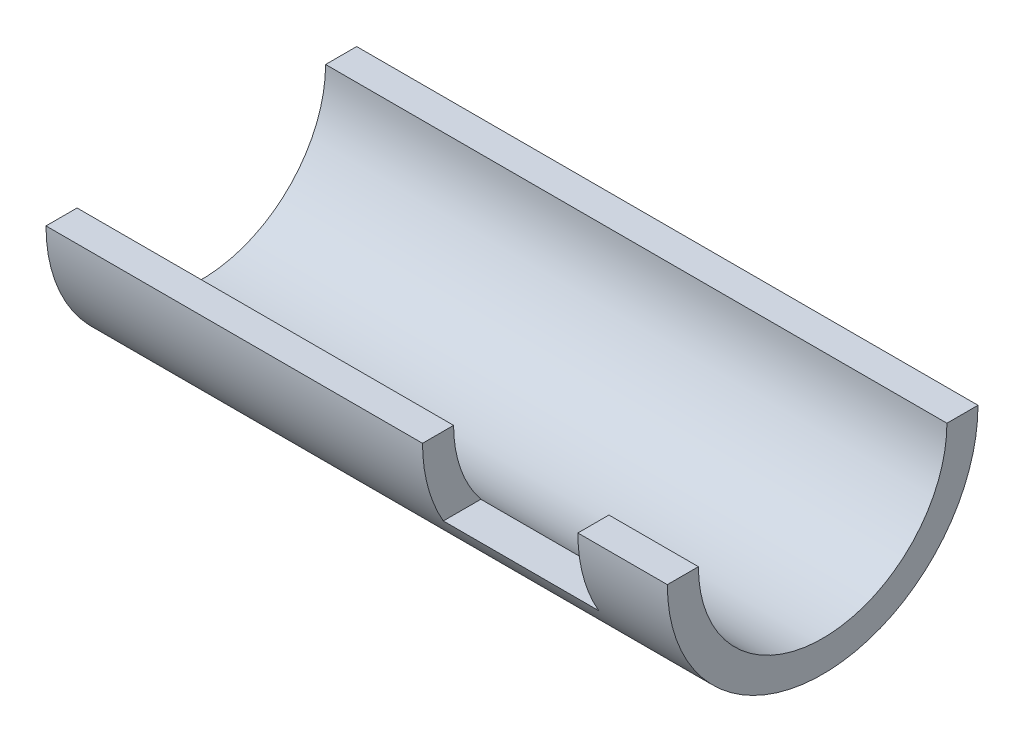
SolidWorks part; units mm, degrees
ref_plane "Front Plane" through (0, 0, 0) normal (0, 0, 1) x (1, 0, 0)
ref_plane "Top Plane" through (0, 0, 0) normal (0, 1, 0) x (1, 0, 0)
ref_plane "Right Plane" through (0, 0, 0) normal (1, 0, 0) x (0, 0, -1)
sketch "Sketch1" plane through (0, 0, 0) normal (1, 0, 0) x (0, 0, -1)
  line L2 (-25.4, 0) -> (-31.75, 0)
  line L3 (31.75, 0) -> (25.4, 0)
  arc A2 (-25.4, 0) -> (25.4, 0) centre (0, 0) ccw
  arc A3 (-31.75, 0) -> (31.75, 0) centre (0, 0) ccw
  dimension "D1" = 31.75
  dimension "D2" = 25.4
  dimension "D3" = 6.35
  dimension "D4" = 6.35
extrude "Boss-Extrude1" add sketch "Sketch1" against normal blind 127
sketch "Sketch2" plane through (0, 0, 0) normal (0, 0, 1) x (1, 0, 0)
  line L0 (-127, 0) -> (0, 0) construction
  line L1 (-50.038, 0) -> (-18.288, 0)
  line L2 (-50.038, 0) -> (-50.038, -15.875)
  line L3 (-50.038, -15.875) -> (-18.288, -15.875)
  line L4 (-18.288, 0) -> (-18.288, -15.875)
  line L5 (-127, 0) -> (-127, -31.75) construction
  dimension "D1" = 31.75
  dimension "D2" = 15.875
  dimension "D3" = 76.962
extrude "Cut-Extrude1" cut sketch "Sketch2" along normal blind 127
